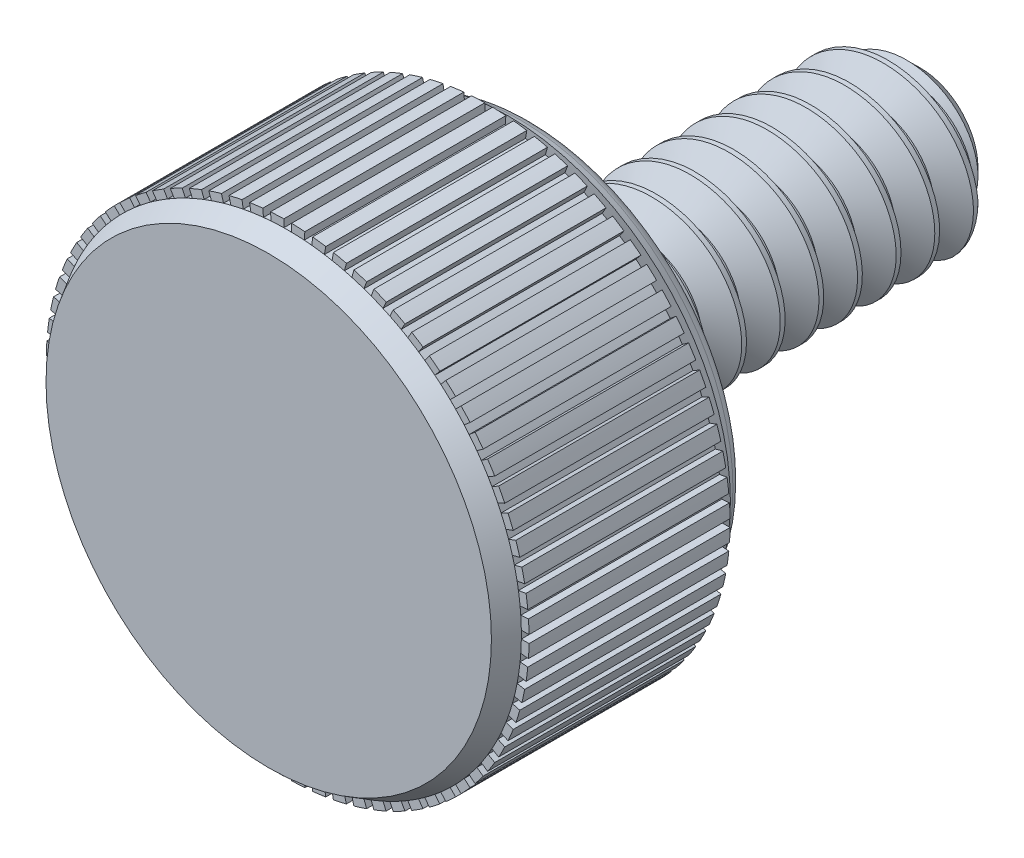
SolidWorks part; units mm, degrees
ref_plane "Front" through (0, 0, 0) normal (0, 0, 1) x (1, 0, 0)
ref_plane "Top" through (0, 0, 0) normal (0, 1, 0) x (1, 0, 0)
ref_plane "Right" through (0, 0, 0) normal (1, 0, 0) x (0, 0, -1)
sketch "Sketch20" plane through (0, 0, 0) normal (1, 0, 0) x (0, 0, -1)
  line L0 (0, 0) -> (6.35, 0) construction
  line L1 (6.35, 1.4224) -> (6.35, -1.4224) construction
  line L2 (0, 3.9688) -> (0, -3.9688) construction
  line L3 (-4.3656, 3.9688) -> (-4.3656, -3.9688) construction
  line L4 (0, 3.5719) -> (0, -3.5719) construction
  point P9 (3.4925, -1.4224)
  point P11 (0, 0)
  point P14 (0, 0)
  dimension "D1" = 2.8448
  dimension "D2" = 6.35
  dimension "D3" = 2.8575
  dimension "Head Height" = 4.3656
  dimension "Shoulder Diameter" = 7.1437
  dimension "Head Diameter" = 7.9375
sketch "Sketch1" plane through (0, 0, 0) normal (0, 0, 1) x (1, 0, 0)
  circle A0 centre (0, 0) radius 1.4224
  dimension "dia" = 2.8448
extrude "Extrude1" add sketch "Sketch1" against normal blind 6.35
chamfer "Chamfer2" distance 0.4763 angle 45 1 edges at (1.4224, 0, -6.35)
sketch "Sketch15" plane through (0, 0, -6.35) normal (0, 0, -1) x (-1, 0, 0)
  circle A0 centre (0, 0) radius 1.4224 construction
  circle A2 centre (0, 0) radius 1.4224
curve "Helix/Spiral1" pitch 0.635 height 6.985 radius 1.4224 centre (0, 0, -6.35) axis (0, 0, 1) start towards (0, 1, 0) parameters "pitch"=0.635
sketch "Sketch14" plane through (0, 0, 0) normal (1, 0, 0) x (0, 0, -1)
  line L0 (6.35, 1.4224) -> (6.9056, 1.4224)
  line L1 (6.9056, 1.4224) -> (6.6675, 1.01)
  line L2 (6.6675, 1.01) -> (6.5881, 1.01)
  line L3 (6.5881, 1.01) -> (6.35, 1.4224)
  line L4 (6.4691, 1.2162) -> (6.7866, 1.2162) construction
  line L5 (6.35, -1.4224) -> (6.35, 1.4224) construction
  dimension "D1" = 0.0794
  dimension "D2" = 0.3175
  dimension "D3" = 60
sweep "Cut-Sweep1" cut profiles "Sketch14" path "Helix/Spiral1"
sketch "Sketch27" plane through (0, 0, 0) normal (0, 0, 1) x (1, 0, 0)
  circle A0 centre (0, 0) radius 3.5719
extrude "Boss-Extrude4" add sketch "Sketch27" along normal blind 0.4366
sketch "Sketch30" plane through (0, 0, 0) normal (0, 0, -1) x (-1, 0, 0)
  circle A0 centre (0, 0) radius 1.4224
extrude "Boss-Extrude5" add sketch "Sketch30" along normal through all draft 20
draft "Draft1" type of draft neutral plane draft angle 20 faces to draft 1 face at (3.5719, 0, 0.4366) neutral plane through (0, 0, 0.4366) neutral plane normal (0, 0, 1) reverse direction yes parameters "D1"=20
fillet "Fillet1" radius 0.3493 1 edges at (3.413, 0, 0)
sketch "Sketch21" plane through (0, 0, 0.4366) normal (0, 0, 1) x (1, 0, 0)
  line L0 (-3.9688, 0) -> (3.9688, 0) construction
  line L1 (-3.9688, 1.5875) -> (3.9688, 1.5875) construction
  line L2 (0, 0) -> (0, 1.5875) construction
  circle A0 centre (0, 0) radius 3.9688
  dimension "D1" = 1.5875
extrude "Boss-Extrude1" add sketch "Sketch21" along normal up to vertex (3.9291 mm away) up to point (0, -3.9688, 4.3656)
ref_plane "Plane1" through (0, 3.9688, 0) normal (0, 1, 0) x (-1, 0, 0)
sketch "Sketch22" plane through (0, 3.9688, 0) normal (0, 1, 0) x (-1, 0, 0)
  line L0 (0, 4.3656) -> (0, 0) construction
  line L1 (-0.0635, 4.3656) -> (0.0635, 4.3656)
  line L3 (-0.0635, 4.3656) -> (-0.0635, 0)
  line L4 (-0.0635, 0) -> (0.0635, 0)
  line L7 (0.0635, 4.3656) -> (0.0635, 0)
  dimension "D1" = 0.127
extrude "Cut-Extrude1" cut sketch "Sketch22" against normal offset from surface (0.1275 mm away) 0.127 up to face at (3.9688, 0, 4.3656) offset beyond the face yes
pattern_circular "CirPattern1" count 72 over 360 about axis through (0, 0, 4.3656) along (0, 0, -1) of "Cut-Extrude1"
sketch "Sketch29" plane through (0, 0, 0) normal (1, 0, 0) x (0, 0, -1)
  line L0 (-4.0538, 3.8417) -> (-4.3656, 3.6617)
  line L1 (-4.3656, 3.6617) -> (-4.3656, 4.0958)
  line L2 (-4.0538, 3.8417) -> (-4.0538, 4.0958)
  line L3 (-4.3656, 4.0958) -> (-4.0538, 4.0958)
  line L4 (-0.4366, -3.5719) -> (-0.4366, 3.5719) construction
  line L5 (0, 0) -> (-2.4011, 0) construction
  line L6 (-4.3656, 3.9688) -> (-0.4366, 3.9688) construction
  line L7 (-2.4011, 3.9688) -> (-2.4011, 0) construction
  line L8 (-0.4366, 4.0958) -> (-0.7484, 4.0958)
  line L9 (-0.7484, 3.8418) -> (-0.7484, 4.0958)
  line L10 (-0.4366, 3.6617) -> (-0.4366, 4.0958)
  line L11 (-0.7484, 3.8418) -> (-0.4366, 3.6617)
  dimension "D1" = 0.127
  dimension "D2" = 30
  dimension "D3" = 0.127
  dimension "D4" = 0.3118
revolve "Cut-Revolve1" cut sketch "Sketch29" angle 360 about L5
equation "\"D3@Helix/Spiral1\" = \"Lg@Extrude1\"+\"pitch@Helix/Spiral1\""
equation "\"D1@Sketch14\" = \"pitch@Helix/Spiral1\" * .125"
equation "\"D2@Sketch14\" = \"pitch@Helix/Spiral1\" * .5"
equation "\"D1@Chamfer2\" = \"pitch@Helix/Spiral1\" * .75"
equation "\"D1@Sketch20\" = \"dia@Sketch1\""
equation "\"D2@Sketch20\" = \"Lg@Extrude1\""
equation "\"D3@Sketch20\" = \"pitch@Helix/Spiral1\"*4.50"
equation "\"D4@Sketch29\" = \"Head Height@Sketch20\"/14"
equation "\"D1@Boss-Extrude4\" = \"Head Height@Sketch20\"*.1"
equation "\"D1@Fillet1\" = \"D1@Boss-Extrude4\"*.8"
